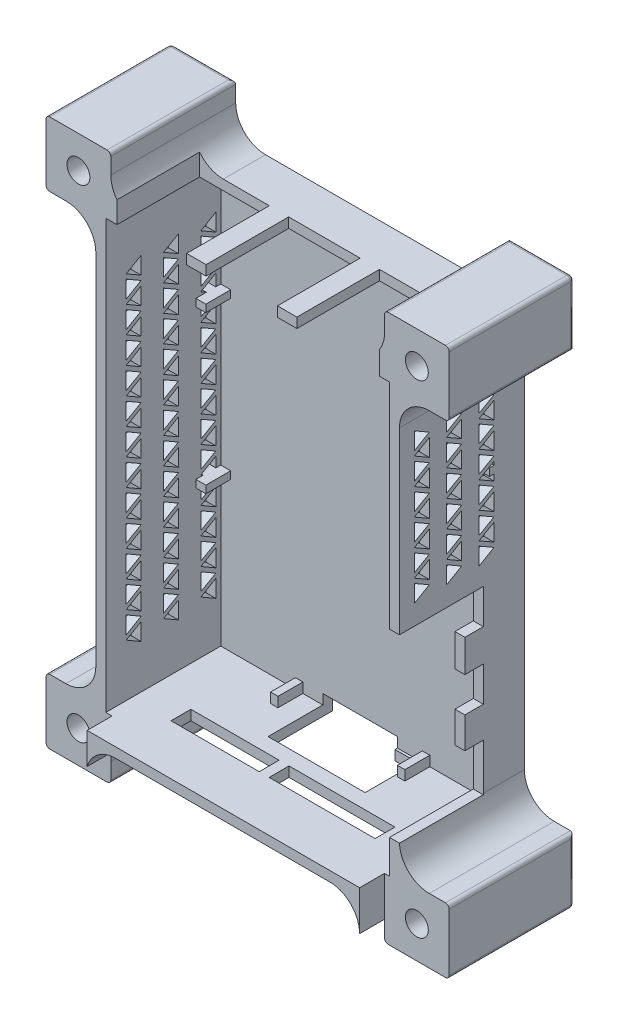
SolidWorks part; units mm, degrees
ref_plane "Front Plane" through (0, 0, 0) normal (0, 0, 1) x (1, 0, 0)
ref_plane "Top Plane" through (0, 0, 0) normal (0, 1, 0) x (1, 0, 0)
ref_plane "Right Plane" through (0, 0, 0) normal (1, 0, 0) x (0, 0, -1)
sketch "Sketch1" plane through (0, 0, 0) normal (0, 0, 1) x (1, 0, 0)
  line L1 (0, 0) -> (61, 0)
  line L2 (0, 0) -> (0, 90)
  line L3 (0, 90) -> (61, 90)
  line L4 (61, 0) -> (61, 90)
  dimension "D1" = 61
  dimension "D2" = 90
extrude "Boss-Extrude1" add sketch "Sketch1" along normal blind 2
sketch "Sketch2" plane through (0, 0, 2) normal (0, 0, 1) x (1, 0, 0)
  line L7 (0, -16.225) -> (0, 16.225) construction
  line L8 (0, 90) -> (0, 0)
  line L9 (2, 90) -> (2, 2)
  line L10 (2, 2) -> (59, 2)
  line L11 (59, 2) -> (59, 90)
  line L12 (2, 88) -> (2, 2)
  line L13 (2, 2) -> (59, 2)
  line L14 (59, 2) -> (59, 88)
  line L15 (0, 0) -> (61, 0)
  line L18 (61, 90) -> (61, 0)
  line L20 (2, 88) -> (59, 88)
  line L21 (0, 90) -> (61, 90)
  dimension "D1" = 2
extrude "Boss-Extrude2" add sketch "Sketch2" along normal blind 6.6
sketch "Sketch3" plane through (0, 0, 2) normal (0, 0, 1) x (1, 0, 0)
  line L0 (59, 2) -> (2, 2) construction
  line L1 (44, 2) -> (42.5, 2)
  line L2 (44, 2) -> (44, 4)
  line L3 (44, 4) -> (42.5, 4)
  line L4 (42.5, 2) -> (42.5, 4)
  line L5 (2, 2) -> (2, 88) construction
  line L6 (17, 2) -> (18.5, 2)
  line L7 (17, 2) -> (17, 4)
  line L8 (17, 4) -> (18.5, 4)
  line L9 (18.5, 2) -> (18.5, 4)
  line L10 (2, 32) -> (4, 32)
  line L11 (2, 32) -> (2, 33.5)
  line L12 (2, 33.5) -> (4, 33.5)
  line L13 (4, 32) -> (4, 33.5)
  line L14 (59, 88) -> (59, 2) construction
  line L15 (59, 32) -> (57, 32)
  line L16 (59, 32) -> (59, 33.5)
  line L17 (59, 33.5) -> (57, 33.5)
  line L18 (57, 32) -> (57, 33.5)
  line L19 (2, 2) -> (2, 88) construction
  line L20 (59, 63.5) -> (57, 63.5)
  line L21 (59, 63.5) -> (59, 65)
  line L22 (59, 65) -> (57, 65)
  line L23 (57, 63.5) -> (57, 65)
  line L24 (2, 63.5) -> (4, 63.5)
  line L25 (2, 63.5) -> (2, 65)
  line L26 (2, 65) -> (4, 65)
  line L27 (4, 63.5) -> (4, 65)
  line L28 (59, 2) -> (2, 2) construction
  dimension "D1" = 1.5
  dimension "D2" = 1.5
  dimension "D3" = 1.5
  dimension "D4" = 1.5
  dimension "D5" = 1.5
  dimension "D6" = 1.5
  dimension "D7" = 2
  dimension "D8" = 2
  dimension "D9" = 2
  dimension "D10" = 2
  dimension "D11" = 2
  dimension "D12" = 2
  dimension "D13" = 30
  dimension "D14" = 30
  dimension "D15" = 30
  dimension "D16" = 30
  dimension "D17" = 15
  dimension "D18" = 15
extrude "Boss-Extrude3" add sketch "Sketch3" along normal blind 5
sketch "Sketch4" plane through (0, 0, 8.6) normal (0, 0, 1) x (1, 0, 0)
  line L1 (61, 90) -> (0, 90)
  line L3 (59, 88) -> (2, 88)
  line L5 (61, 90) -> (61, 0)
  line L6 (0, 90) -> (0, 0)
  line L7 (0, 0) -> (61, 0)
  line L8 (2, 2) -> (59, 2)
  line L9 (2, 88) -> (2, 2)
  line L10 (59, 2) -> (59, 88)
  line L11 (59, 2) -> (59, 88) construction
extrude "Boss-Extrude4" add sketch "Sketch4" along normal blind 16.5
sketch "Sketch5" plane through (0, 90, 0) normal (0, 1, 0) x (1, 0, 0)
  line L1 (57, -8.5) -> (40.4, -8.5)
  line L3 (57, -22.25) -> (40.4, -22.25) construction
  line L4 (40.4, -8.5) -> (40.4, -22.25)
  line L5 (61, 0) -> (0, 0) construction
  line L6 (61, -25.1) -> (0, -25.1) construction
  line L7 (36.5, -25.1) -> (22.15, -25.1)
  line L8 (36.5, -25.1) -> (36.5, -8.5)
  line L9 (36.5, -8.5) -> (22.15, -8.5)
  line L10 (22.15, -25.1) -> (22.15, -8.5)
  line L11 (0, -25.1) -> (0, 0) construction
  line L12 (18.25, -25.1) -> (4.25, -25.1)
  line L13 (18.25, -25.1) -> (18.25, -8.5)
  line L14 (18.25, -8.5) -> (4.25, -8.5)
  line L15 (4.25, -25.1) -> (4.25, -8.5)
  line L17 (57, -25.1) -> (40.4, -25.1)
  line L19 (57, -22.25) -> (40.4, -22.25) construction
  line L20 (40.4, -25.1) -> (40.4, -22.25)
  line L21 (57, -8.5) -> (57, -25.1)
  line L22 (61, -25.1) -> (61, 0) construction
  point P21 (61, -12.55)
  dimension "D2" = 16.6
  dimension "D3" = 13.75
  dimension "D4" = 8.5
  dimension "D5" = 4.25
  dimension "D6" = 3.9
  dimension "D7" = 14
  dimension "D8" = 8.5
  dimension "D9" = 8.5
  dimension "D10" = 3.9
  dimension "D11" = 4
  dimension "D12" = 0
extrude "Cut-Extrude1" cut sketch "Sketch5" against normal blind 2
sketch "Sketch7" plane through (61, 0, 0) normal (1, 0, 0) x (0, 0, -1)
  line L0 (-11.95, 18.25) -> (-11.95, 24.5)
  line L8 (-11.95, 18.25) -> (-8.25, 18.25)
  line L9 (-8.25, 8.75) -> (-8.25, 18.25)
  line L10 (-11.95, 24.5) -> (-8.25, 24.5)
  line L12 (-11.95, 38) -> (-8.25, 38)
  line L14 (-11.95, 31.5) -> (-8.25, 31.5)
  line L18 (-25.1, 0) -> (-25.1, 90) construction
  line L19 (-25.1, 8.75) -> (-25.1, 45)
  line L21 (-11.95, 38) -> (-11.95, 31.5)
  line L22 (-8.25, 8.75) -> (-25.1, 8.75)
  line L23 (-25.1, 45) -> (-8.25, 45)
  line L24 (-25.1, 0) -> (0, 0) construction
  line L25 (-8.25, 24.5) -> (-8.25, 31.5)
  line L26 (-8.25, 38) -> (-8.25, 45)
  line L28 (0, 0) -> (0, 90) construction
  line L47 (-22.1, 79) -> (-19.1, 77.2679)
  line L49 (-19.1, 77.2679) -> (-22.1, 75.5359)
  line L50 (-22.1, 75.5359) -> (-22.1, 79)
  line L141 (-22.1, 74.6121) -> (-19.1, 76.3442)
  line L144 (-19.1, 76.3442) -> (-19.1, 72.8801)
  line L145 (-19.1, 72.8801) -> (-22.1, 74.6121)
  line L146 (-25.1, 90) -> (0, 90) construction
  line L151 (-15.6, 75.5359) -> (-15.6, 79)
  line L152 (-15.6, 79) -> (-12.6, 77.2679)
  line L153 (-12.6, 77.2679) -> (-15.6, 75.5359)
  line L154 (-12.6, 72.8801) -> (-15.6, 74.6121)
  line L155 (-15.6, 74.6121) -> (-12.6, 76.3442)
  line L156 (-12.6, 76.3442) -> (-12.6, 72.8801)
  line L157 (-9.1, 75.5359) -> (-9.1, 79)
  line L158 (-9.1, 79) -> (-6.1, 77.2679)
  line L159 (-6.1, 77.2679) -> (-9.1, 75.5359)
  line L160 (-6.1, 72.8801) -> (-9.1, 74.6121)
  line L161 (-9.1, 74.6121) -> (-6.1, 76.3442)
  line L162 (-6.1, 76.3442) -> (-6.1, 72.8801)
  line L163 (-15.6, 70.2243) -> (-15.6, 73.6884)
  line L164 (-15.6, 73.6884) -> (-12.6, 71.9563)
  line L165 (-12.6, 71.9563) -> (-15.6, 70.2243)
  line L166 (-12.6, 67.5685) -> (-15.6, 69.3005)
  line L167 (-15.6, 69.3005) -> (-12.6, 71.0326)
  line L168 (-12.6, 71.0326) -> (-12.6, 67.5685)
  line L169 (-9.1, 70.2243) -> (-9.1, 73.6884)
  line L170 (-9.1, 73.6884) -> (-6.1, 71.9563)
  line L171 (-6.1, 71.9563) -> (-9.1, 70.2243)
  line L172 (-6.1, 67.5685) -> (-9.1, 69.3005)
  line L173 (-9.1, 69.3005) -> (-6.1, 71.0326)
  line L174 (-6.1, 71.0326) -> (-6.1, 67.5685)
  line L175 (-15.6, 64.9127) -> (-15.6, 68.3768)
  line L176 (-15.6, 68.3768) -> (-12.6, 66.6447)
  line L177 (-12.6, 66.6447) -> (-15.6, 64.9127)
  line L178 (-12.6, 62.2568) -> (-15.6, 63.9889)
  line L179 (-15.6, 63.9889) -> (-12.6, 65.7209)
  line L180 (-12.6, 65.7209) -> (-12.6, 62.2568)
  line L181 (-9.1, 64.9127) -> (-9.1, 68.3768)
  line L182 (-9.1, 68.3768) -> (-6.1, 66.6447)
  line L183 (-6.1, 66.6447) -> (-9.1, 64.9127)
  line L184 (-6.1, 62.2568) -> (-9.1, 63.9889)
  line L185 (-9.1, 63.9889) -> (-6.1, 65.7209)
  line L186 (-6.1, 65.7209) -> (-6.1, 62.2568)
  line L187 (-15.6, 59.601) -> (-15.6, 63.0651)
  line L188 (-15.6, 63.0651) -> (-12.6, 61.3331)
  line L189 (-12.6, 61.3331) -> (-15.6, 59.601)
  line L190 (-12.6, 56.9452) -> (-15.6, 58.6773)
  line L191 (-15.6, 58.6773) -> (-12.6, 60.4093)
  line L192 (-12.6, 60.4093) -> (-12.6, 56.9452)
  line L193 (-9.1, 59.601) -> (-9.1, 63.0651)
  line L194 (-9.1, 63.0651) -> (-6.1, 61.3331)
  line L195 (-6.1, 61.3331) -> (-9.1, 59.601)
  line L196 (-6.1, 56.9452) -> (-9.1, 58.6773)
  line L197 (-9.1, 58.6773) -> (-6.1, 60.4093)
  line L198 (-6.1, 60.4093) -> (-6.1, 56.9452)
  line L199 (-15.6, 54.2894) -> (-15.6, 57.7535)
  line L200 (-15.6, 57.7535) -> (-12.6, 56.0215)
  line L201 (-12.6, 56.0215) -> (-15.6, 54.2894)
  line L202 (-12.6, 51.6336) -> (-15.6, 53.3656)
  line L203 (-15.6, 53.3656) -> (-12.6, 55.0977)
  line L204 (-12.6, 55.0977) -> (-12.6, 51.6336)
  line L205 (-9.1, 54.2894) -> (-9.1, 57.7535)
  line L206 (-9.1, 57.7535) -> (-6.1, 56.0215)
  line L207 (-6.1, 56.0215) -> (-9.1, 54.2894)
  line L208 (-6.1, 51.6336) -> (-9.1, 53.3656)
  line L209 (-9.1, 53.3656) -> (-6.1, 55.0977)
  line L210 (-6.1, 55.0977) -> (-6.1, 51.6336)
  line L211 (-15.6, 48.9778) -> (-15.6, 52.4419)
  line L212 (-15.6, 52.4419) -> (-12.6, 50.7098)
  line L213 (-12.6, 50.7098) -> (-15.6, 48.9778)
  line L217 (-9.1, 48.9778) -> (-9.1, 52.4419)
  line L218 (-9.1, 52.4419) -> (-6.1, 50.7098)
  line L219 (-6.1, 50.7098) -> (-9.1, 48.9778)
  line L223 (-22.1, 70.2243) -> (-22.1, 73.6884)
  line L224 (-22.1, 73.6884) -> (-19.1, 71.9563)
  line L225 (-19.1, 71.9563) -> (-22.1, 70.2243)
  line L226 (-19.1, 67.5685) -> (-22.1, 69.3005)
  line L227 (-22.1, 69.3005) -> (-19.1, 71.0326)
  line L228 (-19.1, 71.0326) -> (-19.1, 67.5685)
  line L229 (-22.1, 64.9127) -> (-22.1, 68.3768)
  line L230 (-22.1, 68.3768) -> (-19.1, 66.6447)
  line L231 (-19.1, 66.6447) -> (-22.1, 64.9127)
  line L232 (-19.1, 62.2568) -> (-22.1, 63.9889)
  line L233 (-22.1, 63.9889) -> (-19.1, 65.7209)
  line L234 (-19.1, 65.7209) -> (-19.1, 62.2568)
  line L235 (-22.1, 59.601) -> (-22.1, 63.0651)
  line L236 (-22.1, 63.0651) -> (-19.1, 61.3331)
  line L237 (-19.1, 61.3331) -> (-22.1, 59.601)
  line L238 (-19.1, 56.9452) -> (-22.1, 58.6773)
  line L239 (-22.1, 58.6773) -> (-19.1, 60.4093)
  line L240 (-19.1, 60.4093) -> (-19.1, 56.9452)
  line L241 (-22.1, 54.2894) -> (-22.1, 57.7535)
  line L242 (-22.1, 57.7535) -> (-19.1, 56.0215)
  line L243 (-19.1, 56.0215) -> (-22.1, 54.2894)
  line L244 (-19.1, 51.6336) -> (-22.1, 53.3656)
  line L245 (-22.1, 53.3656) -> (-19.1, 55.0977)
  line L246 (-19.1, 55.0977) -> (-19.1, 51.6336)
  line L247 (-22.1, 48.9778) -> (-22.1, 52.4419)
  line L248 (-22.1, 52.4419) -> (-19.1, 50.7098)
  line L249 (-19.1, 50.7098) -> (-22.1, 48.9778)
  line L253 (-6.1, 49.7861) -> (-6.1, 46.322) [skipped]
  line L254 (-9.1, 48.054) -> (-6.1, 49.7861) [skipped]
  line L255 (-12.6, 49.7861) -> (-12.6, 46.322) [skipped]
  line L256 (-15.6, 48.054) -> (-12.6, 49.7861) [skipped]
  line L257 (-19.1, 49.7861) -> (-19.1, 46.322) [skipped]
  line L258 (-22.1, 48.054) -> (-19.1, 49.7861) [skipped]
  line L259 (-19.1, 46.322) -> (-22.1, 48.054) [skipped]
  line L260 (-12.6, 46.322) -> (-15.6, 48.054) [skipped]
  line L261 (-6.1, 46.322) -> (-9.1, 48.054) [skipped]
  point P0 (-8.25, 13.5)
  point P16 (-8.25, 41.5)
  point P18 (-10.1, 18.25)
  point P20 (-8.25, 28)
  dimension "D1" = 9.5
  dimension "D2" = 28
  dimension "D3" = 7
  dimension "D4" = 7
  dimension "D5" = 13.5
  dimension "D6" = 41.5
  dimension "D7" = 3.7
  dimension "D8" = 3.7
  dimension "D9" = 8.25
  dimension "D10" = 0
  dimension "D11" = 0
  dimension "D12" = 60
  dimension "D13" = 60
  dimension "D14" = 60
  dimension "D15" = 60
  dimension "D16" = 0.9238
  dimension "D17" = 3
  dimension "D18" = 11
  dimension "D19" = 3
  dimension "D20" = 3
  dimension "D21" = 6
  dimension "D22" = 0.9238
  dimension "D23" = 3
  dimension "D24" = 9.5
sketch "Sketch8" plane through (0, 0, 0) normal (0, -1, 0) x (-1, 0, 0)
  line L0 (0, -25.1) -> (0, 0) construction
  line L2 (-22.5, -13) -> (-22.5, -2.5)
  line L3 (-22.5, -2.5) -> (-42, -2.5)
  line L4 (-42, -13) -> (-42, -2.5)
  line L5 (0, 13.805) -> (0, -13.805) construction
  line L6 (-61, -25.1) -> (-61, 0) construction
  line L7 (-33.55, 0) -> (33.55, 0) construction
  line L8 (-22.5, -13) -> (-42, -13)
  line L9 (-10, -20) -> (-27.72, -20)
  line L10 (-10, -20) -> (-10, -16)
  line L11 (-10, -16) -> (-27.72, -16)
  line L12 (-51, -20) -> (-51, -16)
  line L13 (-27.72, -20) -> (-27.72, -16)
  line L14 (-29.72, -20) -> (-29.72, -16)
  line L15 (-29.72, -20) -> (-51, -20)
  line L16 (-29.72, -16) -> (-51, -16)
  dimension "D1" = 22.5
  dimension "D2" = 19
  dimension "D3" = 2.5
  dimension "D4" = 10.5
  dimension "D5" = 3
  dimension "D6" = 4
  dimension "D7" = 10
  dimension "D8" = 10
  dimension "D9" = 2
  dimension "D10" = 31.28
extrude "Cut-Extrude3" cut sketch "Sketch8" against normal blind 2
sketch "Sketch9" plane through (0, 0, 0) normal (-1, 0, 0) x (0, 0, 1)
  line L0 (3, 78) -> (6, 76.2679)
  line L5 (6, 76.2679) -> (3, 74.5359)
  line L6 (3, 74.5359) -> (3, 78)
  line L7 (3, 73.6121) -> (6, 75.3442)
  line L20 (6, 75.3442) -> (6, 71.8801)
  line L22 (6, 71.8801) -> (3, 73.6121)
  line L24 (0, 90) -> (0, 0) construction
  line L215 (25.1, 90) -> (0, 90) construction
  line L232 (10.5, 74.5359) -> (10.5, 78)
  line L236 (10.5, 78) -> (13.5, 76.2679)
  line L238 (13.5, 76.2679) -> (10.5, 74.5359)
  line L267 (13.5, 71.8801) -> (10.5, 73.6121)
  line L268 (10.5, 73.6121) -> (13.5, 75.3442)
  line L269 (13.5, 75.3442) -> (13.5, 71.8801)
  line L270 (18, 74.5359) -> (18, 78)
  line L271 (18, 78) -> (21, 76.2679)
  line L272 (21, 76.2679) -> (18, 74.5359)
  line L273 (21, 71.8801) -> (18, 73.6121)
  line L274 (18, 73.6121) -> (21, 75.3442)
  line L275 (21, 75.3442) -> (21, 71.8801)
  line L276 (10.5, 69.2243) -> (10.5, 72.6884)
  line L277 (10.5, 72.6884) -> (13.5, 70.9563)
  line L278 (13.5, 70.9563) -> (10.5, 69.2243)
  line L279 (13.5, 66.5685) -> (10.5, 68.3005)
  line L280 (10.5, 68.3005) -> (13.5, 70.0326)
  line L281 (13.5, 70.0326) -> (13.5, 66.5685)
  line L282 (18, 69.2243) -> (18, 72.6884)
  line L283 (18, 72.6884) -> (21, 70.9563)
  line L284 (21, 70.9563) -> (18, 69.2243)
  line L285 (21, 66.5685) -> (18, 68.3005)
  line L286 (18, 68.3005) -> (21, 70.0326)
  line L287 (21, 70.0326) -> (21, 66.5685)
  line L288 (10.5, 63.9127) -> (10.5, 67.3768)
  line L289 (10.5, 67.3768) -> (13.5, 65.6447)
  line L290 (13.5, 65.6447) -> (10.5, 63.9127)
  line L291 (13.5, 61.2568) -> (10.5, 62.9889)
  line L292 (10.5, 62.9889) -> (13.5, 64.7209)
  line L293 (13.5, 64.7209) -> (13.5, 61.2568)
  line L294 (18, 63.9127) -> (18, 67.3768)
  line L295 (18, 67.3768) -> (21, 65.6447)
  line L296 (21, 65.6447) -> (18, 63.9127)
  line L297 (21, 61.2568) -> (18, 62.9889)
  line L298 (18, 62.9889) -> (21, 64.7209)
  line L299 (21, 64.7209) -> (21, 61.2568)
  line L300 (10.5, 58.601) -> (10.5, 62.0651)
  line L301 (10.5, 62.0651) -> (13.5, 60.3331)
  line L302 (13.5, 60.3331) -> (10.5, 58.601)
  line L303 (13.5, 55.9452) -> (10.5, 57.6773)
  line L304 (10.5, 57.6773) -> (13.5, 59.4093)
  line L305 (13.5, 59.4093) -> (13.5, 55.9452)
  line L306 (18, 58.601) -> (18, 62.0651)
  line L307 (18, 62.0651) -> (21, 60.3331)
  line L308 (21, 60.3331) -> (18, 58.601)
  line L309 (21, 55.9452) -> (18, 57.6773)
  line L310 (18, 57.6773) -> (21, 59.4093)
  line L311 (21, 59.4093) -> (21, 55.9452)
  line L312 (10.5, 53.2894) -> (10.5, 56.7535)
  line L313 (10.5, 56.7535) -> (13.5, 55.0215)
  line L314 (13.5, 55.0215) -> (10.5, 53.2894)
  line L315 (13.5, 50.6336) -> (10.5, 52.3656)
  line L316 (10.5, 52.3656) -> (13.5, 54.0977)
  line L317 (13.5, 54.0977) -> (13.5, 50.6336)
  line L318 (18, 53.2894) -> (18, 56.7535)
  line L319 (18, 56.7535) -> (21, 55.0215)
  line L320 (21, 55.0215) -> (18, 53.2894)
  line L321 (21, 50.6336) -> (18, 52.3656)
  line L322 (18, 52.3656) -> (21, 54.0977)
  line L323 (21, 54.0977) -> (21, 50.6336)
  line L324 (10.5, 47.9778) -> (10.5, 51.4419)
  line L325 (10.5, 51.4419) -> (13.5, 49.7098)
  line L326 (13.5, 49.7098) -> (10.5, 47.9778)
  line L327 (13.5, 45.322) -> (10.5, 47.054)
  line L328 (10.5, 47.054) -> (13.5, 48.7861)
  line L329 (13.5, 48.7861) -> (13.5, 45.322)
  line L330 (18, 47.9778) -> (18, 51.4419)
  line L331 (18, 51.4419) -> (21, 49.7098)
  line L332 (21, 49.7098) -> (18, 47.9778)
  line L333 (21, 45.322) -> (18, 47.054)
  line L334 (18, 47.054) -> (21, 48.7861)
  line L335 (21, 48.7861) -> (21, 45.322)
  line L336 (10.5, 42.6662) -> (10.5, 46.1303)
  line L337 (10.5, 46.1303) -> (13.5, 44.3982)
  line L338 (13.5, 44.3982) -> (10.5, 42.6662)
  line L339 (13.5, 40.0104) -> (10.5, 41.7424)
  line L340 (10.5, 41.7424) -> (13.5, 43.4745)
  line L341 (13.5, 43.4745) -> (13.5, 40.0104)
  line L342 (18, 42.6662) -> (18, 46.1303)
  line L343 (18, 46.1303) -> (21, 44.3982)
  line L344 (21, 44.3982) -> (18, 42.6662)
  line L345 (21, 40.0104) -> (18, 41.7424)
  line L346 (18, 41.7424) -> (21, 43.4745)
  line L347 (21, 43.4745) -> (21, 40.0104)
  line L348 (10.5, 37.3545) -> (10.5, 40.8186)
  line L349 (10.5, 40.8186) -> (13.5, 39.0866)
  line L350 (13.5, 39.0866) -> (10.5, 37.3545)
  line L351 (13.5, 34.6987) -> (10.5, 36.4308)
  line L352 (10.5, 36.4308) -> (13.5, 38.1628)
  line L353 (13.5, 38.1628) -> (13.5, 34.6987)
  line L354 (18, 37.3545) -> (18, 40.8186)
  line L355 (18, 40.8186) -> (21, 39.0866)
  line L356 (21, 39.0866) -> (18, 37.3545)
  line L357 (21, 34.6987) -> (18, 36.4308)
  line L358 (18, 36.4308) -> (21, 38.1628)
  line L359 (21, 38.1628) -> (21, 34.6987)
  line L360 (10.5, 32.0429) -> (10.5, 35.507)
  line L361 (10.5, 35.507) -> (13.5, 33.775)
  line L362 (13.5, 33.775) -> (10.5, 32.0429)
  line L363 (13.5, 29.3871) -> (10.5, 31.1192)
  line L364 (10.5, 31.1192) -> (13.5, 32.8512)
  line L365 (13.5, 32.8512) -> (13.5, 29.3871)
  line L366 (18, 32.0429) -> (18, 35.507)
  line L367 (18, 35.507) -> (21, 33.775)
  line L368 (21, 33.775) -> (18, 32.0429)
  line L369 (21, 29.3871) -> (18, 31.1192)
  line L370 (18, 31.1192) -> (21, 32.8512)
  line L371 (21, 32.8512) -> (21, 29.3871)
  line L372 (10.5, 26.7313) -> (10.5, 30.1954)
  line L373 (10.5, 30.1954) -> (13.5, 28.4633)
  line L374 (13.5, 28.4633) -> (10.5, 26.7313)
  line L375 (13.5, 24.0755) -> (10.5, 25.8075)
  line L376 (10.5, 25.8075) -> (13.5, 27.5396)
  line L377 (13.5, 27.5396) -> (13.5, 24.0755)
  line L378 (18, 26.7313) -> (18, 30.1954)
  line L379 (18, 30.1954) -> (21, 28.4633)
  line L380 (21, 28.4633) -> (18, 26.7313)
  line L381 (21, 24.0755) -> (18, 25.8075)
  line L382 (18, 25.8075) -> (21, 27.5396)
  line L383 (21, 27.5396) -> (21, 24.0755)
  line L384 (10.5, 21.4197) -> (10.5, 24.8838)
  line L385 (10.5, 24.8838) -> (13.5, 23.1517)
  line L386 (13.5, 23.1517) -> (10.5, 21.4197)
  line L387 (13.5, 18.7639) -> (10.5, 20.4959)
  line L388 (10.5, 20.4959) -> (13.5, 22.228)
  line L389 (13.5, 22.228) -> (13.5, 18.7639)
  line L390 (18, 21.4197) -> (18, 24.8838)
  line L391 (18, 24.8838) -> (21, 23.1517)
  line L392 (21, 23.1517) -> (18, 21.4197)
  line L393 (21, 18.7639) -> (18, 20.4959)
  line L394 (18, 20.4959) -> (21, 22.228)
  line L395 (21, 22.228) -> (21, 18.7639)
  line L396 (10.5, 16.1081) -> (10.5, 19.5722)
  line L397 (10.5, 19.5722) -> (13.5, 17.8401)
  line L398 (13.5, 17.8401) -> (10.5, 16.1081)
  line L399 (13.5, 13.4522) -> (10.5, 15.1843)
  line L400 (10.5, 15.1843) -> (13.5, 16.9163)
  line L401 (13.5, 16.9163) -> (13.5, 13.4522)
  line L402 (18, 16.1081) -> (18, 19.5722)
  line L403 (18, 19.5722) -> (21, 17.8401)
  line L404 (21, 17.8401) -> (18, 16.1081)
  line L405 (21, 13.4522) -> (18, 15.1843)
  line L406 (18, 15.1843) -> (21, 16.9163)
  line L407 (21, 16.9163) -> (21, 13.4522)
  line L408 (10.5, 10.7964) -> (10.5, 14.2605)
  line L409 (10.5, 14.2605) -> (13.5, 12.5285)
  line L410 (13.5, 12.5285) -> (10.5, 10.7964)
  line L414 (18, 10.7964) -> (18, 14.2605)
  line L415 (18, 14.2605) -> (21, 12.5285)
  line L416 (21, 12.5285) -> (18, 10.7964)
  line L420 (3, 69.2243) -> (3, 72.6884)
  line L421 (3, 72.6884) -> (6, 70.9563)
  line L422 (6, 70.9563) -> (3, 69.2243)
  line L423 (6, 66.5685) -> (3, 68.3005)
  line L424 (3, 68.3005) -> (6, 70.0326)
  line L425 (6, 70.0326) -> (6, 66.5685)
  line L426 (3, 63.9127) -> (3, 67.3768)
  line L427 (3, 67.3768) -> (6, 65.6447)
  line L428 (6, 65.6447) -> (3, 63.9127)
  line L429 (6, 61.2568) -> (3, 62.9889)
  line L430 (3, 62.9889) -> (6, 64.7209)
  line L431 (6, 64.7209) -> (6, 61.2568)
  line L432 (3, 58.601) -> (3, 62.0651)
  line L433 (3, 62.0651) -> (6, 60.3331)
  line L434 (6, 60.3331) -> (3, 58.601)
  line L435 (6, 55.9452) -> (3, 57.6773)
  line L436 (3, 57.6773) -> (6, 59.4093)
  line L437 (6, 59.4093) -> (6, 55.9452)
  line L438 (3, 53.2894) -> (3, 56.7535)
  line L439 (3, 56.7535) -> (6, 55.0215)
  line L440 (6, 55.0215) -> (3, 53.2894)
  line L441 (6, 50.6336) -> (3, 52.3656)
  line L442 (3, 52.3656) -> (6, 54.0977)
  line L443 (6, 54.0977) -> (6, 50.6336)
  line L444 (3, 47.9778) -> (3, 51.4419)
  line L445 (3, 51.4419) -> (6, 49.7098)
  line L446 (6, 49.7098) -> (3, 47.9778)
  line L447 (6, 45.322) -> (3, 47.054)
  line L448 (3, 47.054) -> (6, 48.7861)
  line L449 (6, 48.7861) -> (6, 45.322)
  line L450 (3, 42.6662) -> (3, 46.1303)
  line L451 (3, 46.1303) -> (6, 44.3982)
  line L452 (6, 44.3982) -> (3, 42.6662)
  line L453 (6, 40.0104) -> (3, 41.7424)
  line L454 (3, 41.7424) -> (6, 43.4745)
  line L455 (6, 43.4745) -> (6, 40.0104)
  line L456 (3, 37.3545) -> (3, 40.8186)
  line L457 (3, 40.8186) -> (6, 39.0866)
  line L458 (6, 39.0866) -> (3, 37.3545)
  line L459 (6, 34.6987) -> (3, 36.4308)
  line L460 (3, 36.4308) -> (6, 38.1628)
  line L461 (6, 38.1628) -> (6, 34.6987)
  line L462 (3, 32.0429) -> (3, 35.507)
  line L463 (3, 35.507) -> (6, 33.775)
  line L464 (6, 33.775) -> (3, 32.0429)
  line L465 (6, 29.3871) -> (3, 31.1192)
  line L466 (3, 31.1192) -> (6, 32.8512)
  line L467 (6, 32.8512) -> (6, 29.3871)
  line L468 (3, 26.7313) -> (3, 30.1954)
  line L469 (3, 30.1954) -> (6, 28.4633)
  line L470 (6, 28.4633) -> (3, 26.7313)
  line L471 (6, 24.0755) -> (3, 25.8075)
  line L472 (3, 25.8075) -> (6, 27.5396)
  line L473 (6, 27.5396) -> (6, 24.0755)
  line L474 (3, 21.4197) -> (3, 24.8838)
  line L475 (3, 24.8838) -> (6, 23.1517)
  line L476 (6, 23.1517) -> (3, 21.4197)
  line L477 (6, 18.7639) -> (3, 20.4959)
  line L478 (3, 20.4959) -> (6, 22.228)
  line L479 (6, 22.228) -> (6, 18.7639)
  line L480 (3, 16.1081) -> (3, 19.5722)
  line L481 (3, 19.5722) -> (6, 17.8401)
  line L482 (6, 17.8401) -> (3, 16.1081)
  line L483 (6, 13.4522) -> (3, 15.1843)
  line L484 (3, 15.1843) -> (6, 16.9163)
  line L485 (6, 16.9163) -> (6, 13.4522)
  line L486 (3, 10.7964) -> (3, 14.2605)
  line L487 (3, 14.2605) -> (6, 12.5285)
  line L488 (6, 12.5285) -> (3, 10.7964)
  line L492 (6, 11.6047) -> (6, 8.1406) [skipped]
  line L493 (6, 8.1406) -> (3, 9.8727) [skipped]
  line L494 (3, 9.8727) -> (6, 11.6047) [skipped]
  line L495 (10.5, 9.8727) -> (13.5, 11.6047) [skipped]
  line L496 (13.5, 8.1406) -> (10.5, 9.8727) [skipped]
  line L497 (13.5, 11.6047) -> (13.5, 8.1406) [skipped]
  line L498 (21, 8.1406) -> (18, 9.8727) [skipped]
  line L499 (18, 9.8727) -> (21, 11.6047) [skipped]
  line L500 (21, 11.6047) -> (21, 8.1406) [skipped]
  point P10 (4.5, 72.7461)
  dimension "D1" = 60
  dimension "D2" = 60
  dimension "D3" = 12
  dimension "D4" = 3
  dimension "D5" = 0.8
  dimension "D6" = 60
  dimension "D7" = 3
  dimension "D8" = 10.5
  dimension "D9" = 3
  dimension "D10" = 13
  dimension "D11" = 0.8
  dimension "D12" = 3
extrude "Cut-Extrude22" cut sketch "Sketch9" against normal blind 2
sketch "Sketch10" plane through (0, 0, 25.1) normal (0, 0, 1) x (1, 0, 0)
  line L0 (61, 0) -> (61, 8.75) construction
  line L1 (0, 0) -> (61, 0)
  line L2 (0, 0) -> (0, 2)
  line L3 (0, 2) -> (61, 2)
  line L4 (61, 0) -> (61, 2)
  dimension "D1" = 2
extrude "Boss-Extrude5" add sketch "Sketch10" along normal blind 5
sketch "Sketch20" plane through (0, 0, 0) normal (0, 0, -1) x (-1, 0, 0)
  line L0 (-61, 90) -> (0, 90) construction
  line L1 (-3, 3) -> (10, 3)
  line L2 (-3, 3) -> (-3, -10)
  line L3 (-3, -10) -> (10, -10)
  line L4 (10, 3) -> (10, -10)
  line L5 (-3, 3) -> (10, -10) construction
  line L6 (-3, -10) -> (10, 3) construction
  line L7 (-58, 87) -> (-71, 87)
  line L8 (-58, 87) -> (-58, 100)
  line L9 (-58, 100) -> (-71, 100)
  line L10 (-71, 87) -> (-71, 100)
  line L11 (-58, 87) -> (-71, 100) construction
  line L12 (-58, 100) -> (-71, 87) construction
  line L13 (-61, 0) -> (-61, 90) construction
  line L14 (0, 0) -> (-61, 0) construction
  line L15 (0, 90) -> (0, 0) construction
  point P4 (3.5, -3.5)
  point P9 (-64.5, 93.5)
  dimension "D1" = 3
  dimension "D2" = 3
  dimension "D3" = 13
  dimension "D4" = 13
  dimension "D5" = 3
  dimension "D6" = 13
  dimension "D7" = 3
  dimension "D8" = 13
extrude "Boss-Extrude8" add sketch "Sketch20" against normal up to surface (25.1 mm away) up to face at (2.0833, 60, 25.1)
sketch "Sketch25" plane through (0, 0, 25.1) normal (0, 0, 1) x (1, 0, 0)
  line L1 (3, 3) -> (-10, 3)
  line L2 (3, 3) -> (3, -10)
  line L3 (3, -10) -> (-10, -10)
  line L4 (-10, 3) -> (-10, -10)
  line L5 (3, 3) -> (-10, -10) construction
  line L6 (3, -10) -> (-10, 3) construction
  line L7 (3, -10) -> (3.25, -10)
  line L8 (3, -10) -> (3, 3)
  line L9 (3, 3) -> (3.25, 3)
  line L10 (3.25, -10) -> (3.25, 3)
  line L11 (3, -10) -> (3.25, 3) construction
  line L12 (3, 3) -> (3.25, -10) construction
  point P4 (-3.5, -3.5)
  point P10 (3.125, -3.5)
  dimension "D1" = 0.25
extrude "Cut-Extrude11" cut sketch "Sketch25" along normal through all contours L2 L1 L4 L3 | L8 L7 L10 L9
sketch "Sketch26" plane through (0, 0, 25.1) normal (0, 0, 1) x (1, 0, 0)
  line L1 (3, 3) -> (2, 3)
  line L2 (3, 3) -> (3, 2)
  line L3 (3, 2) -> (2, 2)
  line L4 (2, 3) -> (2, 2)
  line L5 (3, 3) -> (2, 2) construction
  line L6 (3, 2) -> (2, 3) construction
  line L7 (58, 87) -> (59, 87)
  line L8 (58, 87) -> (58, 88)
  line L9 (58, 88) -> (59, 88)
  line L10 (59, 87) -> (59, 88)
  line L11 (58, 87) -> (59, 88) construction
  line L12 (58, 88) -> (59, 87) construction
  point P4 (2.5, 2.5)
  point P10 (58.5, 87.5)
  dimension "D1" = 1
  dimension "D2" = 1
  dimension "D3" = 1
  dimension "D4" = 1
extrude "Cut-Extrude12" cut sketch "Sketch26" against normal up to surface (23.1 mm away) up to face at (30.5, 36.25, 2)
sketch "Sketch27" plane through (0, 0, 25.1) normal (0, 0, 1) x (1, 0, 0)
  line L0 (64.5, 100) -> (64.5, 87) construction
  line L1 (58, 100) -> (71, 100) construction
  line L2 (71, 87) -> (61, 87) construction
  line L3 (71, 93.5) -> (58, 93.5) construction
  line L4 (71, 100) -> (71, 87) construction
  line L5 (58, 90) -> (58, 100) construction
  line L6 (-3.5, -10) -> (-3.5, 3) construction
  line L7 (3, -10) -> (-10, -10) construction
  line L8 (-10, 3) -> (0, 3) construction
  line L9 (-10, -3.5) -> (3, -3.5) construction
  line L10 (-10, -10) -> (-10, 3) construction
  line L11 (3, 0) -> (3, -10) construction
  circle A0 centre (-3.5, -3.5) radius 2.3
  circle A1 centre (64.5, 93.5) radius 2.3
  dimension "D1" = 4.6
  dimension "D2" = 4.6
extrude "Cut-Extrude13" cut sketch "Sketch27" against normal through all
sketch "Sketch31" plane through (0, 0, 0) normal (0, 0, -1) x (-1, 0, 0)
  line L0 (-71, 100) -> (-71, 87) construction
  line L1 (-61.8731, 88.95) -> (-59.2461, 93.5)
  line L2 (-59.2461, 93.5) -> (-61.8731, 98.05)
  line L3 (-61.8731, 98.05) -> (-67.1269, 98.05)
  line L4 (-67.1269, 98.05) -> (-69.7539, 93.5)
  line L5 (-69.7539, 93.5) -> (-67.1269, 88.95)
  line L6 (-67.1269, 88.95) -> (-61.8731, 88.95)
  line L7 (6.1269, -8.05) -> (8.7539, -3.5)
  line L8 (8.7539, -3.5) -> (6.1269, 1.05)
  line L9 (6.1269, 1.05) -> (0.8731, 1.05)
  line L10 (0.8731, 1.05) -> (-1.7539, -3.5)
  line L11 (-1.7539, -3.5) -> (0.8731, -8.05)
  line L12 (0.8731, -8.05) -> (6.1269, -8.05)
  line L13 (10, -10) -> (10, 3) construction
  circle A0 centre (-64.5, 93.5) radius 4.55 construction
  circle A1 centre (3.5, -3.5) radius 4.55 construction
  dimension "D1" = 9.1
  dimension "D2" = 9.1
  dimension "D3" = 30
  dimension "D4" = 30
extrude "Cut-Extrude17" cut sketch "Sketch31" against normal blind 6
fillet "Fillet3" radius 6 1 edges at (58, 90, 12.55) type face fillet first side face at (29.5687, 90, 15.7375) second side face at (58, 95, 12.55)
sketch "Sketch33" plane through (0, 0, 25.1) normal (0, 0, 1) x (1, 0, 0)
  line L0 (2, 2) -> (3.25, 2) construction
  line L1 (3.25, 0) -> (3, 0)
  line L2 (3.25, 0) -> (3.25, 2)
  line L3 (3.25, 2) -> (3, 2)
  line L4 (3, 0) -> (3, 2)
  line L5 (3.25, 0) -> (3, 2) construction
  line L6 (3.25, 2) -> (3, 0) construction
  point P4 (3.125, 1)
  dimension "D1" = 0.25
fillet "Fillet7" radius 6 1 edges at (3, 0, 12.55) type face fillet first side face at (3, -5, 12.55) second side face at (18.86, 0, 18)
sketch "Sketch34" plane through (0, 0, 25.1) normal (0, 0, 1) x (1, 0, 0)
  line L0 (18.25, 90) -> (4.25, 90) construction
  line L1 (59, 3) -> (71, 3)
  line L2 (58, 2) -> (58, -10)
  line L3 (58, -10) -> (71, -10)
  line L4 (71, 3) -> (71, -10)
  line L5 (59, 2) -> (71, -10) construction
  line L6 (58, -10) -> (71, 3) construction
  line L7 (2, 87) -> (-10, 87)
  line L8 (3, 88) -> (3, 100)
  line L9 (3, 100) -> (-10, 100)
  line L10 (-10, 87) -> (-10, 100)
  line L11 (2, 88) -> (-10, 100) construction
  line L12 (3, 100) -> (-10, 87) construction
  line L13 (0, 90) -> (0, 3) construction
  line L14 (61, 0) -> (61, 2) construction
  line L15 (9, 0) -> (61, 0) construction
  line L16 (59, 88) -> (2, 88) construction
  line L17 (2, 88) -> (2, 2) construction
  line L18 (3, 88) -> (2, 88)
  line L19 (2, 88) -> (2, 87)
  line L20 (59, 2) -> (59, 88) construction
  line L21 (44, 2) -> (59, 2) construction
  line L22 (59, 2) -> (59, 3)
  line L23 (58, 2) -> (59, 2)
  point P4 (64.5, -3.5)
  point P9 (-3.5, 93.5)
  dimension "D1" = 3
  dimension "D2" = 3
  dimension "D3" = 3
  dimension "D4" = 3
  dimension "D5" = 13
  dimension "D6" = 13
  dimension "D7" = 13
  dimension "D8" = 13
extrude "Boss-Extrude11" add sketch "Sketch34" against normal up to surface (25.1 mm away) up to face at (30.5, 45, 0)
sketch "Sketch35" plane through (0, 0, 25.1) normal (0, 0, 1) x (1, 0, 0)
  line L0 (-3.5, 100) -> (-3.5, 87) construction
  line L1 (3, 100) -> (-10, 100) construction
  line L2 (-10, 87) -> (0, 87) construction
  line L3 (-10, 93.5) -> (3, 93.5) construction
  line L4 (-10, 100) -> (-10, 87) construction
  line L5 (3, 90) -> (3, 100) construction
  line L6 (64.5, -10) -> (64.5, 3) construction
  line L7 (58, -10) -> (71, -10) construction
  line L8 (71, 3) -> (61, 3) construction
  line L9 (71, -3.5) -> (58, -3.5) construction
  line L10 (71, -10) -> (71, 3) construction
  line L11 (58, 0) -> (58, -10) construction
  circle A0 centre (-3.5, 93.5) radius 2.3
  circle A1 centre (64.5, -3.5) radius 2.3
  dimension "D1" = 4.6
  dimension "D2" = 4.6
extrude "Cut-Extrude18" cut sketch "Sketch35" against normal through all
fillet "Fillet10" radius 6 1 edges at (3, 90, 12.55) type face fillet first side face at (3, 95, 12.55) second side face at (25.2214, 90, 14.4)
fillet "Fillet13" radius 0.75 20 edges at (71, -3.5, 0) (64.5, -10, 0) (-3.5, -10, 0) (-10, -3.5, 0) (-10, 93.5, 0) (-3.5, 100, 0) (71, 93.5, 0) (64.5, 100, 0) (71, 87, 12.55) (71, 100, 12.55) (58, 100, 12.55) (3, 100, 12.55) (-10, 100, 12.55) (-10, 87, 12.55) (-10, 3, 12.55) (-10, -10, 12.55) (3, -10, 12.55) (71, 3, 12.55) (58, -10, 12.55) (71, -10, 12.55)
sketch "Sketch36" plane through (0, 0, 0) normal (0, 0, -1) x (-1, 0, 0)
  line L0 (10, 99.25) -> (10, 87.75) construction
  line L1 (-59.2461, -3.5) -> (-61.8731, 1.05)
  line L2 (-61.8731, 1.05) -> (-67.1269, 1.05)
  line L3 (-67.1269, 1.05) -> (-69.7539, -3.5)
  line L4 (-69.7539, -3.5) -> (-67.1269, -8.05)
  line L5 (-67.1269, -8.05) -> (-61.8731, -8.05)
  line L6 (-61.8731, -8.05) -> (-59.2461, -3.5)
  line L7 (-1.7539, 93.5) -> (0.8731, 88.95)
  line L8 (0.8731, 88.95) -> (6.1269, 88.95)
  line L9 (6.1269, 88.95) -> (8.7539, 93.5)
  line L10 (8.7539, 93.5) -> (6.1269, 98.05)
  line L11 (6.1269, 98.05) -> (0.8731, 98.05)
  line L12 (0.8731, 98.05) -> (-1.7539, 93.5)
  line L15 (-70.25, 3) -> (-70.25, -9.25) construction
  circle A0 centre (-64.5, -3.5) radius 4.55 construction
  circle A1 centre (3.5, 93.5) radius 4.55 construction
  dimension "D1" = 30
  dimension "D2" = 30
  dimension "D3" = 9.1
  dimension "D4" = 9.1
extrude "Cut-Extrude19" cut sketch "Sketch36" against normal blind 6
sketch "Sketch38" plane through (0, 0, 25.1) normal (0, 0, 1) x (1, 0, 0)
  line L0 (61, 2) -> (3.25, 2) construction
  line L1 (69, -8) -> (58, -8)
  line L2 (69, -8) -> (69, 3)
  line L3 (69, 3) -> (58, 3)
  line L4 (58, -8) -> (58, 3)
  line L6 (61, 0) -> (61, 2) construction
  dimension "D1" = 11
  dimension "D2" = 8
  dimension "D3" = 1
extrude "Cut-Extrude20" cut sketch "Sketch38" along normal blind 10
fillet "Fillet14" radius 6 1 edges at (58, 0, 12.55) type face fillet first side face at (40.36, 0, 18) second side face at (58, -4.625, 12.55)
sketch "Sketch39" plane through (0, 0, 0) normal (0, -1, 0) x (1, 0, 0)
  line L0 (9, 0) -> (52, 0) construction
  line L1 (22.5, 2.5) -> (37.5, 2.5)
  line L2 (22.5, 2.5) -> (22.5, 0)
  line L3 (22.5, 0) -> (37.5, 0)
  line L4 (37.5, 2.5) -> (37.5, 0)
  dimension "D1" = 15
extrude "Cut-Extrude21" cut sketch "Sketch39" against normal blind 4
fillet "Fillet17" radius 6 1 edges at (0, 87, 12.55) type face fillet first side face at (0, 70.9563, 19) second side face at (-4.625, 87, 12.55)
fillet "Fillet18" radius 6 1 edges at (0, 3, 12.55) type face fillet first side face at (0, 70.9563, 19) second side face at (-4.625, 3, 12.55)
sketch "Sketch43" plane through (0, 0, 0) normal (-1, 0, 0) x (0, 0, 1)
  line L0 (6, 61.2568) -> (6, 64.7209) construction
  line L1 (3, 33.5) -> (6, 33.5)
  line L2 (3, 33.5) -> (3, 32)
  line L3 (3, 32) -> (6, 32)
  line L4 (6, 33.5) -> (6, 32)
  line L5 (3, 33.5) -> (6, 32) construction
  line L6 (3, 32) -> (6, 33.5) construction
  line L7 (3, 65) -> (6, 65)
  line L8 (3, 65) -> (3, 63.5)
  line L9 (3, 63.5) -> (6, 63.5)
  line L10 (6, 65) -> (6, 63.5)
  line L11 (3, 65) -> (6, 63.5) construction
  line L12 (3, 63.5) -> (6, 65) construction
  line L13 (6, 63.5) -> (6, 64.7209) construction
  point P4 (4.5, 32.75)
  point P11 (4.5, 64.25)
  dimension "D1" = 1.5
extrude "Boss-Extrude15" add sketch "Sketch43" against normal up to surface (2 mm away) up to face at (2, 47.9663, 5.8221)
extrude "Cut-Extrude23" cut sketch "Sketch7" against normal blind 2
sketch "Sketch44" plane through (61, 0, 0) normal (1, 0, 0) x (0, 0, -1)
  line L1 (-7, 65) -> (-6.1, 65)
  line L2 (-7, 65) -> (-7, 63.5)
  line L3 (-7, 63.5) -> (-6.1, 63.5)
  line L4 (-6.1, 65) -> (-6.1, 63.5)
  line L5 (-7, 65) -> (-6.1, 63.5) construction
  line L6 (-7, 63.5) -> (-6.1, 65) construction
  point P4 (-6.55, 64.25)
extrude "Boss-Extrude16" add sketch "Sketch44" against normal up to surface (2 mm away) up to face at (59, 50.7098, 21.1)
fillet "Fillet19" radius 6 1 edges at (61, 3, 12.55) type face fillet first side face at (61, 66.6447, 21.1) second side face at (65.625, 3, 12.55)
fillet "Fillet20" radius 6 1 edges at (61, 87, 12.55) type face fillet first side face at (61, 66.6447, 21.1) second side face at (65.625, 87, 12.55)
